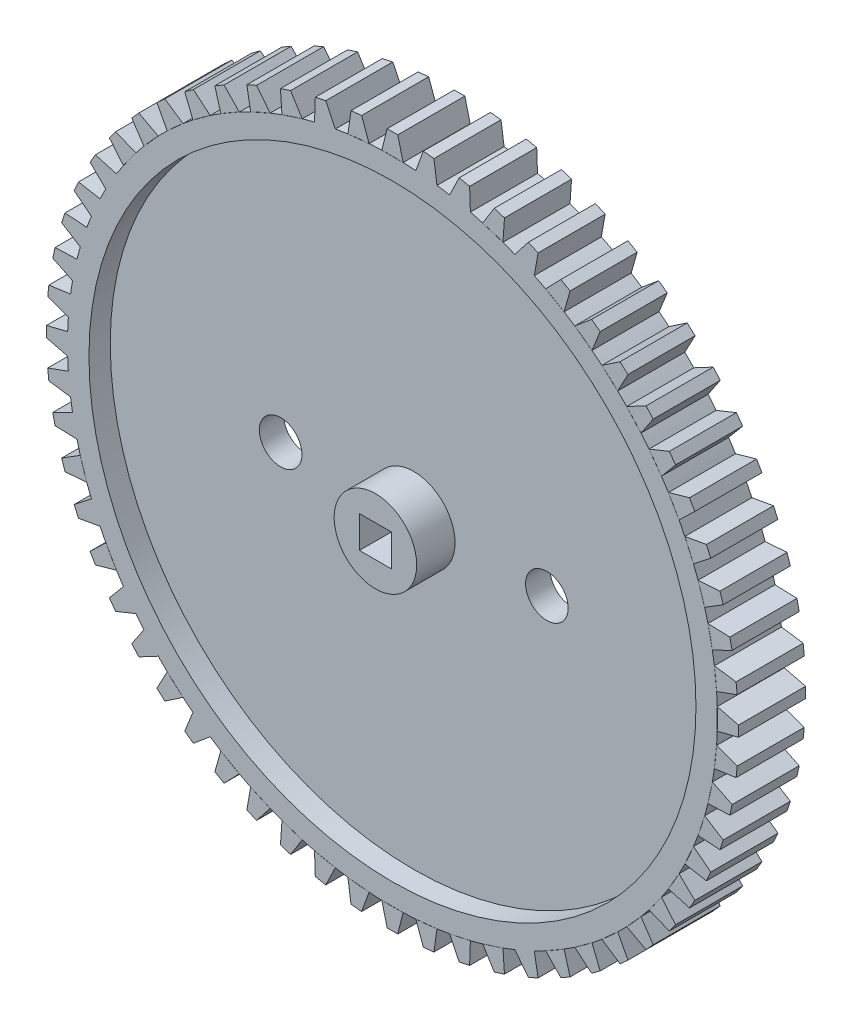
SolidWorks part; units mm, degrees
ref_plane "Front Plane" through (0, 0, 0) normal (0, 0, 1) x (1, 0, 0)
ref_plane "Top Plane" through (0, 0, 0) normal (0, 1, 0) x (1, 0, 0)
ref_plane "Right Plane" through (0, 0, 0) normal (1, 0, 0) x (0, 0, -1)
sketch "Sketch1" plane through (0, 0, 0) normal (0, 0, 1) x (1, 0, 0)
  line L0 (0, 40.9888) -> (0, -63.3022) construction
  line L1 (-1.5, -1.5) -> (1.5, -1.5)
  line L2 (-1.5, -1.5) -> (-1.5, 1.5)
  line L3 (-1.5, 1.5) -> (1.5, 1.5)
  line L4 (1.5, -1.5) -> (1.5, 1.5)
  line L5 (-1.5, -1.5) -> (1.5, 1.5) construction
  line L6 (-1.5, 1.5) -> (1.5, -1.5) construction
  line L7 (-1, 30.4962) -> (1, 30.4962)
  line L8 (1, 30.4962) -> (0.5, 32.4962)
  line L9 (0.5, 32.4962) -> (-0.5, 32.4962)
  line L10 (-0.5, 32.4962) -> (-1, 30.4962)
  line L11 (3.894, 32.2659) -> (2.8995, 32.3704)
  line L12 (2.1932, 30.4336) -> (4.1822, 30.2246)
  line L13 (4.1822, 30.2246) -> (3.894, 32.2659)
  line L14 (2.8995, 32.3704) -> (2.1932, 30.4336)
  line L15 (7.2454, 31.6821) -> (6.2673, 31.89)
  line L16 (5.3624, 30.0377) -> (7.3187, 29.6218)
  line L17 (7.3187, 29.6218) -> (7.2454, 31.6821)
  line L18 (6.2673, 31.89) -> (5.3624, 30.0377)
  line L19 (10.5174, 30.7512) -> (9.5663, 31.0602)
  line L20 (8.4728, 29.3126) -> (10.3749, 28.6945)
  line L21 (10.3749, 28.6945) -> (10.5174, 30.7512)
  line L22 (9.5663, 31.0602) -> (8.4728, 29.3126)
  line L23 (13.6741, 29.4833) -> (12.7606, 29.8901)
  line L24 (11.4904, 28.2664) -> (13.3174, 27.4529)
  line L25 (13.3174, 27.4529) -> (13.6741, 29.4833)
  line L26 (12.7606, 29.8901) -> (11.4904, 28.2664)
  line L27 (16.6811, 27.8925) -> (15.8151, 28.3925)
  line L28 (14.3821, 26.9104) -> (16.1141, 25.9104)
  line L29 (16.1141, 25.9104) -> (16.6811, 27.8925)
  line L30 (15.8151, 28.3925) -> (14.3821, 26.9104)
  line L31 (19.5053, 25.996) -> (18.6963, 26.5838)
  line L32 (17.1162, 25.2597) -> (18.7342, 24.0841)
  line L33 (18.7342, 24.0841) -> (19.5053, 25.996)
  line L34 (18.6963, 26.5838) -> (17.1162, 25.2597)
  line L35 (22.1157, 23.8148) -> (21.3726, 24.4839)
  line L36 (19.6628, 23.3322) -> (21.1491, 21.9939)
  line L37 (21.1491, 21.9939) -> (22.1157, 23.8148)
  line L38 (21.3726, 24.4839) -> (19.6628, 23.3322)
  line L39 (24.4839, 21.3726) -> (23.8148, 22.1157)
  line L40 (21.9939, 21.1491) -> (23.3322, 19.6628)
  line L41 (23.3322, 19.6628) -> (24.4839, 21.3726)
  line L42 (23.8148, 22.1157) -> (21.9939, 21.1491)
  line L43 (26.5838, 18.6963) -> (25.996, 19.5053)
  line L44 (24.0841, 18.7342) -> (25.2597, 17.1162)
  line L45 (25.2597, 17.1162) -> (26.5838, 18.6963)
  line L46 (25.996, 19.5053) -> (24.0841, 18.7342)
  line L47 (28.3925, 15.8151) -> (27.8925, 16.6811)
  line L48 (25.9104, 16.1141) -> (26.9104, 14.3821)
  line L49 (26.9104, 14.3821) -> (28.3925, 15.8151)
  line L50 (27.8925, 16.6811) -> (25.9104, 16.1141)
  line L51 (29.8901, 12.7606) -> (29.4833, 13.6741)
  line L52 (27.4529, 13.3174) -> (28.2664, 11.4904)
  line L53 (28.2664, 11.4904) -> (29.8901, 12.7606)
  line L54 (29.4833, 13.6741) -> (27.4529, 13.3174)
  line L55 (31.0602, 9.5663) -> (30.7512, 10.5174)
  line L56 (28.6945, 10.3749) -> (29.3126, 8.4728)
  line L57 (29.3126, 8.4728) -> (31.0602, 9.5663)
  line L58 (30.7512, 10.5174) -> (28.6945, 10.3749)
  line L59 (31.89, 6.2673) -> (31.6821, 7.2454)
  line L60 (29.6218, 7.3187) -> (30.0377, 5.3624)
  line L61 (30.0377, 5.3624) -> (31.89, 6.2673)
  line L62 (31.6821, 7.2454) -> (29.6218, 7.3187)
  line L63 (32.3704, 2.8995) -> (32.2659, 3.894)
  line L64 (30.2246, 4.1822) -> (30.4336, 2.1932)
  line L65 (30.4336, 2.1932) -> (32.3704, 2.8995)
  line L66 (32.2659, 3.894) -> (30.2246, 4.1822)
  line L67 (32.4962, -0.5) -> (32.4962, 0.5)
  line L68 (30.4962, 1) -> (30.4962, -1)
  line L69 (30.4962, -1) -> (32.4962, -0.5)
  line L70 (32.4962, 0.5) -> (30.4962, 1)
  line L71 (32.2659, -3.894) -> (32.3704, -2.8995)
  line L72 (30.4336, -2.1932) -> (30.2246, -4.1822)
  line L73 (30.2246, -4.1822) -> (32.2659, -3.894)
  line L74 (32.3704, -2.8995) -> (30.4336, -2.1932)
  line L75 (31.6821, -7.2454) -> (31.89, -6.2673)
  line L76 (30.0377, -5.3624) -> (29.6218, -7.3187)
  line L77 (29.6218, -7.3187) -> (31.6821, -7.2454)
  line L78 (31.89, -6.2673) -> (30.0377, -5.3624)
  line L79 (30.7512, -10.5174) -> (31.0602, -9.5663)
  line L80 (29.3126, -8.4728) -> (28.6945, -10.3749)
  line L81 (28.6945, -10.3749) -> (30.7512, -10.5174)
  line L82 (31.0602, -9.5663) -> (29.3126, -8.4728)
  line L83 (29.4833, -13.6741) -> (29.8901, -12.7606)
  line L84 (28.2664, -11.4904) -> (27.4529, -13.3174)
  line L85 (27.4529, -13.3174) -> (29.4833, -13.6741)
  line L86 (29.8901, -12.7606) -> (28.2664, -11.4904)
  line L87 (27.8925, -16.6811) -> (28.3925, -15.8151)
  line L88 (26.9104, -14.3821) -> (25.9104, -16.1141)
  line L89 (25.9104, -16.1141) -> (27.8925, -16.6811)
  line L90 (28.3925, -15.8151) -> (26.9104, -14.3821)
  line L91 (25.996, -19.5053) -> (26.5838, -18.6963)
  line L92 (25.2597, -17.1162) -> (24.0841, -18.7342)
  line L93 (24.0841, -18.7342) -> (25.996, -19.5053)
  line L94 (26.5838, -18.6963) -> (25.2597, -17.1162)
  line L95 (23.8148, -22.1157) -> (24.4839, -21.3726)
  line L96 (23.3322, -19.6628) -> (21.9939, -21.1491)
  line L97 (21.9939, -21.1491) -> (23.8148, -22.1157)
  line L98 (24.4839, -21.3726) -> (23.3322, -19.6628)
  line L99 (21.3726, -24.4839) -> (22.1157, -23.8148)
  line L100 (21.1491, -21.9939) -> (19.6628, -23.3322)
  line L101 (19.6628, -23.3322) -> (21.3726, -24.4839)
  line L102 (22.1157, -23.8148) -> (21.1491, -21.9939)
  line L103 (18.6963, -26.5838) -> (19.5053, -25.996)
  line L104 (18.7342, -24.0841) -> (17.1162, -25.2597)
  line L105 (17.1162, -25.2597) -> (18.6963, -26.5838)
  line L106 (19.5053, -25.996) -> (18.7342, -24.0841)
  line L107 (15.8151, -28.3925) -> (16.6811, -27.8925)
  line L108 (16.1141, -25.9104) -> (14.3821, -26.9104)
  line L109 (14.3821, -26.9104) -> (15.8151, -28.3925)
  line L110 (16.6811, -27.8925) -> (16.1141, -25.9104)
  line L111 (12.7606, -29.8901) -> (13.6741, -29.4833)
  line L112 (13.3174, -27.4529) -> (11.4904, -28.2664)
  line L113 (11.4904, -28.2664) -> (12.7606, -29.8901)
  line L114 (13.6741, -29.4833) -> (13.3174, -27.4529)
  line L115 (9.5663, -31.0602) -> (10.5174, -30.7512)
  line L116 (10.3749, -28.6945) -> (8.4728, -29.3126)
  line L117 (8.4728, -29.3126) -> (9.5663, -31.0602)
  line L118 (10.5174, -30.7512) -> (10.3749, -28.6945)
  line L119 (6.2673, -31.89) -> (7.2454, -31.6821)
  line L120 (7.3187, -29.6218) -> (5.3624, -30.0377)
  line L121 (5.3624, -30.0377) -> (6.2673, -31.89)
  line L122 (7.2454, -31.6821) -> (7.3187, -29.6218)
  line L123 (2.8995, -32.3704) -> (3.894, -32.2659)
  line L124 (4.1822, -30.2246) -> (2.1932, -30.4336)
  line L125 (2.1932, -30.4336) -> (2.8995, -32.3704)
  line L126 (3.894, -32.2659) -> (4.1822, -30.2246)
  line L127 (-0.5, -32.4962) -> (0.5, -32.4962)
  line L128 (1, -30.4962) -> (-1, -30.4962)
  line L129 (-1, -30.4962) -> (-0.5, -32.4962)
  line L130 (0.5, -32.4962) -> (1, -30.4962)
  line L131 (-3.894, -32.2659) -> (-2.8995, -32.3704)
  line L132 (-2.1932, -30.4336) -> (-4.1822, -30.2246)
  line L133 (-4.1822, -30.2246) -> (-3.894, -32.2659)
  line L134 (-2.8995, -32.3704) -> (-2.1932, -30.4336)
  line L135 (-7.2454, -31.6821) -> (-6.2673, -31.89)
  line L136 (-5.3624, -30.0377) -> (-7.3187, -29.6218)
  line L137 (-7.3187, -29.6218) -> (-7.2454, -31.6821)
  line L138 (-6.2673, -31.89) -> (-5.3624, -30.0377)
  line L139 (-10.5174, -30.7512) -> (-9.5663, -31.0602)
  line L140 (-8.4728, -29.3126) -> (-10.3749, -28.6945)
  line L141 (-10.3749, -28.6945) -> (-10.5174, -30.7512)
  line L142 (-9.5663, -31.0602) -> (-8.4728, -29.3126)
  line L143 (-13.6741, -29.4833) -> (-12.7606, -29.8901)
  line L144 (-11.4904, -28.2664) -> (-13.3174, -27.4529)
  line L145 (-13.3174, -27.4529) -> (-13.6741, -29.4833)
  line L146 (-12.7606, -29.8901) -> (-11.4904, -28.2664)
  line L147 (-16.6811, -27.8925) -> (-15.8151, -28.3925)
  line L148 (-14.3821, -26.9104) -> (-16.1141, -25.9104)
  line L149 (-16.1141, -25.9104) -> (-16.6811, -27.8925)
  line L150 (-15.8151, -28.3925) -> (-14.3821, -26.9104)
  line L151 (-19.5053, -25.996) -> (-18.6963, -26.5838)
  line L152 (-17.1162, -25.2597) -> (-18.7342, -24.0841)
  line L153 (-18.7342, -24.0841) -> (-19.5053, -25.996)
  line L154 (-18.6963, -26.5838) -> (-17.1162, -25.2597)
  line L155 (-22.1157, -23.8148) -> (-21.3726, -24.4839)
  line L156 (-19.6628, -23.3322) -> (-21.1491, -21.9939)
  line L157 (-21.1491, -21.9939) -> (-22.1157, -23.8148)
  line L158 (-21.3726, -24.4839) -> (-19.6628, -23.3322)
  line L159 (-24.4839, -21.3726) -> (-23.8148, -22.1157)
  line L160 (-21.9939, -21.1491) -> (-23.3322, -19.6628)
  line L161 (-23.3322, -19.6628) -> (-24.4839, -21.3726)
  line L162 (-23.8148, -22.1157) -> (-21.9939, -21.1491)
  line L163 (-26.5838, -18.6963) -> (-25.996, -19.5053)
  line L164 (-24.0841, -18.7342) -> (-25.2597, -17.1162)
  line L165 (-25.2597, -17.1162) -> (-26.5838, -18.6963)
  line L166 (-25.996, -19.5053) -> (-24.0841, -18.7342)
  line L167 (-28.3925, -15.8151) -> (-27.8925, -16.6811)
  line L168 (-25.9104, -16.1141) -> (-26.9104, -14.3821)
  line L169 (-26.9104, -14.3821) -> (-28.3925, -15.8151)
  line L170 (-27.8925, -16.6811) -> (-25.9104, -16.1141)
  line L171 (-29.8901, -12.7606) -> (-29.4833, -13.6741)
  line L172 (-27.4529, -13.3174) -> (-28.2664, -11.4904)
  line L173 (-28.2664, -11.4904) -> (-29.8901, -12.7606)
  line L174 (-29.4833, -13.6741) -> (-27.4529, -13.3174)
  line L175 (-31.0602, -9.5663) -> (-30.7512, -10.5174)
  line L176 (-28.6945, -10.3749) -> (-29.3126, -8.4728)
  line L177 (-29.3126, -8.4728) -> (-31.0602, -9.5663)
  line L178 (-30.7512, -10.5174) -> (-28.6945, -10.3749)
  line L179 (-31.89, -6.2673) -> (-31.6821, -7.2454)
  line L180 (-29.6218, -7.3187) -> (-30.0377, -5.3624)
  line L181 (-30.0377, -5.3624) -> (-31.89, -6.2673)
  line L182 (-31.6821, -7.2454) -> (-29.6218, -7.3187)
  line L183 (-32.3704, -2.8995) -> (-32.2659, -3.894)
  line L184 (-30.2246, -4.1822) -> (-30.4336, -2.1932)
  line L185 (-30.4336, -2.1932) -> (-32.3704, -2.8995)
  line L186 (-32.2659, -3.894) -> (-30.2246, -4.1822)
  line L187 (-32.4962, 0.5) -> (-32.4962, -0.5)
  line L188 (-30.4962, -1) -> (-30.4962, 1)
  line L189 (-30.4962, 1) -> (-32.4962, 0.5)
  line L190 (-32.4962, -0.5) -> (-30.4962, -1)
  line L191 (-32.2659, 3.894) -> (-32.3704, 2.8995)
  line L192 (-30.4336, 2.1932) -> (-30.2246, 4.1822)
  line L193 (-30.2246, 4.1822) -> (-32.2659, 3.894)
  line L194 (-32.3704, 2.8995) -> (-30.4336, 2.1932)
  line L195 (-31.6821, 7.2454) -> (-31.89, 6.2673)
  line L196 (-30.0377, 5.3624) -> (-29.6218, 7.3187)
  line L197 (-29.6218, 7.3187) -> (-31.6821, 7.2454)
  line L198 (-31.89, 6.2673) -> (-30.0377, 5.3624)
  line L199 (-30.7512, 10.5174) -> (-31.0602, 9.5663)
  line L200 (-29.3126, 8.4728) -> (-28.6945, 10.3749)
  line L201 (-28.6945, 10.3749) -> (-30.7512, 10.5174)
  line L202 (-31.0602, 9.5663) -> (-29.3126, 8.4728)
  line L203 (-29.4833, 13.6741) -> (-29.8901, 12.7606)
  line L204 (-28.2664, 11.4904) -> (-27.4529, 13.3174)
  line L205 (-27.4529, 13.3174) -> (-29.4833, 13.6741)
  line L206 (-29.8901, 12.7606) -> (-28.2664, 11.4904)
  line L207 (-27.8925, 16.6811) -> (-28.3925, 15.8151)
  line L208 (-26.9104, 14.3821) -> (-25.9104, 16.1141)
  line L209 (-25.9104, 16.1141) -> (-27.8925, 16.6811)
  line L210 (-28.3925, 15.8151) -> (-26.9104, 14.3821)
  line L211 (-25.996, 19.5053) -> (-26.5838, 18.6963)
  line L212 (-25.2597, 17.1162) -> (-24.0841, 18.7342)
  line L213 (-24.0841, 18.7342) -> (-25.996, 19.5053)
  line L214 (-26.5838, 18.6963) -> (-25.2597, 17.1162)
  line L215 (-23.8148, 22.1157) -> (-24.4839, 21.3726)
  line L216 (-23.3322, 19.6628) -> (-21.9939, 21.1491)
  line L217 (-21.9939, 21.1491) -> (-23.8148, 22.1157)
  line L218 (-24.4839, 21.3726) -> (-23.3322, 19.6628)
  line L219 (-21.3726, 24.4839) -> (-22.1157, 23.8148)
  line L220 (-21.1491, 21.9939) -> (-19.6628, 23.3322)
  line L221 (-19.6628, 23.3322) -> (-21.3726, 24.4839)
  line L222 (-22.1157, 23.8148) -> (-21.1491, 21.9939)
  line L223 (-18.6963, 26.5838) -> (-19.5053, 25.996)
  line L224 (-18.7342, 24.0841) -> (-17.1162, 25.2597)
  line L225 (-17.1162, 25.2597) -> (-18.6963, 26.5838)
  line L226 (-19.5053, 25.996) -> (-18.7342, 24.0841)
  line L227 (-15.8151, 28.3925) -> (-16.6811, 27.8925)
  line L228 (-16.1141, 25.9104) -> (-14.3821, 26.9104)
  line L229 (-14.3821, 26.9104) -> (-15.8151, 28.3925)
  line L230 (-16.6811, 27.8925) -> (-16.1141, 25.9104)
  line L231 (-12.7606, 29.8901) -> (-13.6741, 29.4833)
  line L232 (-13.3174, 27.4529) -> (-11.4904, 28.2664)
  line L233 (-11.4904, 28.2664) -> (-12.7606, 29.8901)
  line L234 (-13.6741, 29.4833) -> (-13.3174, 27.4529)
  line L235 (-9.5663, 31.0602) -> (-10.5174, 30.7512)
  line L236 (-10.3749, 28.6945) -> (-8.4728, 29.3126)
  line L237 (-8.4728, 29.3126) -> (-9.5663, 31.0602)
  line L238 (-10.5174, 30.7512) -> (-10.3749, 28.6945)
  line L239 (-6.2673, 31.89) -> (-7.2454, 31.6821)
  line L240 (-7.3187, 29.6218) -> (-5.3624, 30.0377)
  line L241 (-5.3624, 30.0377) -> (-6.2673, 31.89)
  line L242 (-7.2454, 31.6821) -> (-7.3187, 29.6218)
  line L243 (-2.8995, 32.3704) -> (-3.894, 32.2659)
  line L244 (-4.1822, 30.2246) -> (-2.1932, 30.4336)
  line L245 (-2.1932, 30.4336) -> (-2.8995, 32.3704)
  line L246 (-3.894, 32.2659) -> (-4.1822, 30.2246)
  circle A0 centre (0, 0) radius 32.5
  circle A1 centre (-12.5, 0) radius 2
  circle A2 centre (12.5, 0) radius 2
  circle A3 centre (0, 0) radius 30.5125
  point P15 (0, 30.4962)
  point P18 (0, 32.4962)
  point P258 (0, 0)
  dimension "D1" = 65
  dimension "D2" = 4
  dimension "D4" = 11
  dimension "D3" = 3
  dimension "D5" = 1
  dimension "D6" = 2
  dimension "D7" = 2
  dimension "D8" = 60
extrude "Boss-Extrude1" add sketch "Sketch1" along normal blind 6.3 contours L68 A3 L64 L60 L56 L52 L48 L44 L40 L36 L32 L28 L24 L20 L16 L12 L7 L244 L240 L236 L232 L228 L224 L220 L216 L212 L208 | A3 L237 L235 L238 | A3 L233 L231 L234 | A3 L229 L227 L230 | A3 L225 L223 L226 | A3 L221 L219 L222 | A3 L217 L215 L218 | A3 L213 L211 L214 | A3 L177 L175 L178 | A3 L169 L167 L170 | A3 L157 L155 L158 | A3 L149 L147 L150 | A3 L145 L143 L146 | A3 L141 L139 L142 | A3 L137 L135 L138 | A3 L133 L131 L134 | A3 L129 L127 L130 | A3 L125 L123 L126 | A3 L121 L119 L122 | A3 L117 L115 L118 | A3 L109 L107 L110 | A3 L105 L103 L106 | A3 L101 L99 L102 | A3 L97 L95 L98 | A3 L93 L91 L94 | A3 L89 L87 L90 | A3 L85 L83 L86 | A3 L81 L79 L82 | A3 L77 L75 L78 | A3 L73 L71 L74 | A3 L69 L67 L70 | A3 L65 L63 L66 | A3 L61 L59 L62 | A3 L57 L55 L58 | A3 L53 L51 L54 | A3 L49 L47 L50 | A3 L45 L43 L46 | A3 L41 L39 L42 | A3 L37 L35 L38 | A3 L33 L31 L34 | A3 L29 L27 L30 | A3 L21 L19 L22 | A3 L8 L9 L10 | A3 L245 L243 L246 | L209 L207 L210 L208 | L204 L205 L203 L206 | L200 L201 L199 L202 | L196 L197 L195 L198 | L192 L193 L191 L194 | L190 L188 L189 L187 | L184 L185 L183 L186 | L181 L179 L182 L180 | L172 L173 L171 L174 | L166 L164 L165 L163 | L160 L161 L159 L162 | L153 L151 L154 L152 | L112 L113 L111 L114 | L25 L23 L26 L24 | L16 L17 L15 L18 | L12 L13 L11 L14 | L240 L241 L239 L242 region at (0, 31.3915, 0) region at (0, 29.6336, 0) region at (-3.2813, 31.2196, 0) region at (-9.7005, 29.8551, 0) region at (9.7005, 29.8551, 0) region at (-12.7681, 28.6776, 0) region at (-15.6958, 27.1859, 0) region at (15.6958, 27.1859, 0) region at (-18.4515, 25.3963, 0) region at (18.4515, 25.3963, 0) region at (-21.005, 23.3284, 0) region at (21.005, 23.3284, 0) region at (-23.3284, 21.005, 0) region at (23.3284, 21.005, 0) region at (-25.3963, 18.4515, 0) region at (25.3963, 18.4515, 0) region at (27.1859, 15.6958, 0) region at (28.6776, 12.7681, 0) region at (29.8551, 9.7005, 0) region at (30.7055, 6.5267, 0) region at (31.2196, 3.2813, 0) region at (31.3915, 0, 0) region at (31.2196, -3.2813, 0) region at (30.7055, -6.5267, 0) region at (-29.8551, -9.7005, 0) region at (29.8551, -9.7005, 0) region at (28.6776, -12.7681, 0) region at (-27.1859, -15.6958, 0) region at (27.1859, -15.6958, 0) region at (25.3963, -18.4515, 0) region at (23.3284, -21.005, 0) region at (-21.005, -23.3284, 0) region at (21.005, -23.3284, 0) region at (18.4515, -25.3963, 0) region at (-15.6958, -27.1859, 0) region at (15.6958, -27.1859, 0) region at (-12.7681, -28.6776, 0) region at (-9.7005, -29.8551, 0) region at (9.7005, -29.8551, 0) region at (-6.5267, -30.7055, 0) region at (6.5267, -30.7055, 0) region at (-3.2813, -31.2196, 0) region at (3.2813, -31.2196, 0) region at (0, -31.3915, 0)
sketch "Sketch2" plane through (0, 0, 6.3) normal (0, 0, 1) x (1, 0, 0)
  circle A0 centre (0, 0) radius 32.5 construction
  circle A2 centre (0, 0) radius 28.5
  circle A3 centre (0, 0) radius 3.875
  dimension "D1" = 4
  dimension "D2" = 7.75
extrude "Cut-Extrude1" cut sketch "Sketch2" against normal blind 2
sketch "Sketch3" plane through (0, 0, 0) normal (0, 0, -1) x (-1, 0, 0)
  circle A0 centre (0, 0) radius 32.4962
  circle A1 centre (0, 0) radius 28.4962
  circle A2 centre (0, 0) radius 3.875
  dimension "D1" = 64.9923
  dimension "D3" = 7.75
  dimension "D2" = 4
extrude "Cut-Extrude2" cut sketch "Sketch3" against normal blind 2 contours A1 A2 region at (27.6902, 0, 0)
sketch "Sketch4" plane through (0, 0, 6.3) normal (0, 0, 1) x (1, 0, 0)
  line L1 (-1.5, -1.5) -> (1.5, -1.5)
  line L2 (-1.5, -1.5) -> (-1.5, 1.5)
  line L3 (-1.5, 1.5) -> (1.5, 1.5)
  line L4 (1.5, -1.5) -> (1.5, 1.5)
  circle A0 centre (0, 0) radius 3.875
  dimension "D1" = 7.75
extrude "Boss-Extrude3" add sketch "Sketch4" along normal blind 1.6
sketch "Sketch5" plane through (0, 0, 0) normal (0, 0, -1) x (-1, 0, 0)
  line L1 (-1.5, -1.5) -> (1.5, -1.5)
  line L2 (-1.5, -1.5) -> (-1.5, 1.5)
  line L3 (-1.5, 1.5) -> (1.5, 1.5)
  line L4 (1.5, -1.5) -> (1.5, 1.5)
  circle A0 centre (0, 0) radius 3.875
  dimension "D1" = 7.75
extrude "Boss-Extrude4" add sketch "Sketch5" along normal blind 1.6
